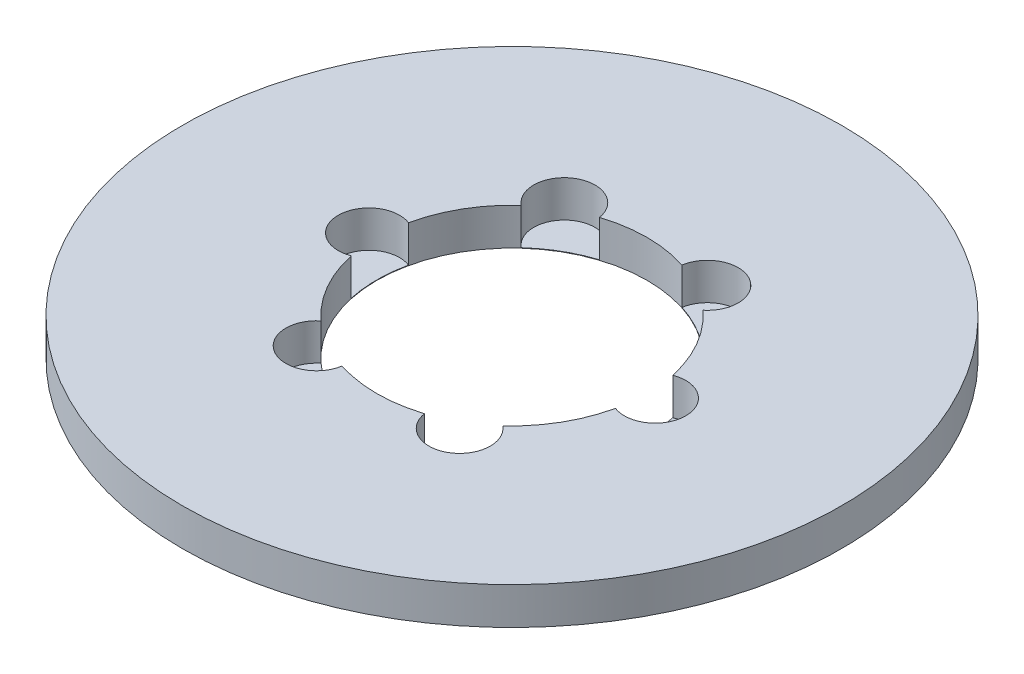
SolidWorks part; units mm, degrees
ref_plane "Front Plane" through (0, 0, 0) normal (0, 0, 1) x (1, 0, 0)
ref_plane "Top Plane" through (0, 0, 0) normal (0, 1, 0) x (1, 0, 0)
ref_plane "Right Plane" through (0, 0, 0) normal (1, 0, 0) x (0, 0, -1)
sketch "Sketch1" plane through (0, 0, 0) normal (0, 1, 0) x (1, 0, 0)
  circle A0 centre (0, 0) radius 97.5
  dimension "FLANGE_OD" = 195
extrude "Boss-Extrude1" add sketch "Sketch1" along normal blind 11
sketch "Sketch2" plane through (0, 0, 0) normal (0, 1, 0) x (1, 0, 0)
  circle A0 centre (0, 0) radius 40
  dimension "BORE_D" = 80
extrude "Cut-Extrude1" cut sketch "Sketch2" along normal through all
sketch "Sketch3" plane through (0, 11, 0) normal (0, 1, 0) x (1, 0, 0)
  circle A0 centre (0, 0) radius 42.3323 construction
  circle A1 centre (-42.3323, 0) radius 9.0763
  dimension "BOLT_D" = 18.1526
  dimension "BOLT_PCD" = 84.6646
extrude "Cut-Extrude2" cut sketch "Sketch3" against normal blind 10.8655
pattern_circular "CirPattern1" count 6 over 360 about axis through (0, 0, 0) along (0, 1, 0) of "Cut-Extrude2"
